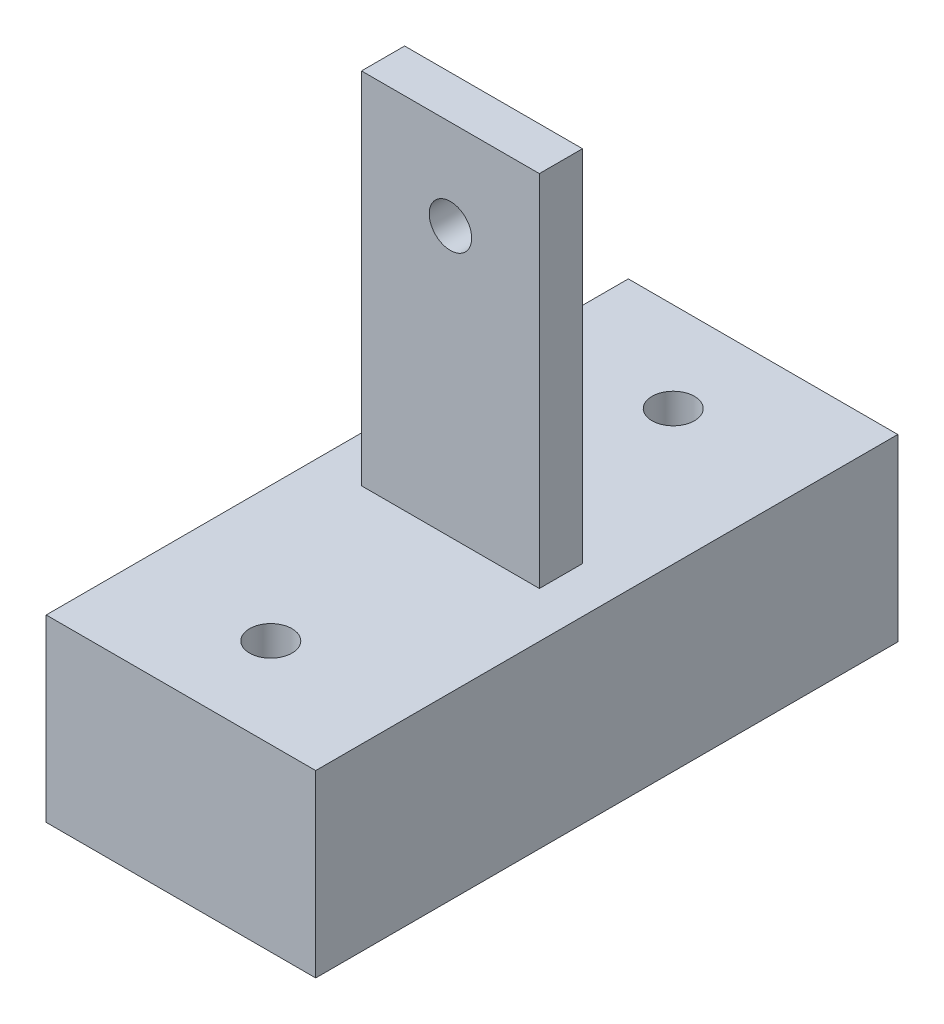
SolidWorks part; units mm, degrees
ref_plane "Front Plane" through (0, 0, 0) normal (0, 0, 1) x (1, 0, 0)
ref_plane "Top Plane" through (0, 0, 0) normal (0, 1, 0) x (1, 0, 0)
ref_plane "Right Plane" through (0, 0, 0) normal (1, 0, 0) x (0, 0, -1)
sketch "Sketch1" plane through (0, 0, 0) normal (1, 0, 0) x (0, 0, -1)
  line L1 (-20.574, 12.7) -> (20.574, 12.7)
  line L2 (-20.574, 12.7) -> (-20.574, 0)
  line L3 (-20.574, 0) -> (20.574, 0)
  line L4 (20.574, 12.7) -> (20.574, 0)
  line L5 (-1.524, 12.7) -> (1.524, 12.7)
  line L6 (-1.524, 12.7) -> (-1.524, 38.1)
  line L7 (-1.524, 38.1) -> (1.524, 38.1)
  line L8 (1.524, 12.7) -> (1.524, 38.1)
  point P10 (0, 38.1)
  point P14 (0, 0)
  dimension "D1" = 12.7
  dimension "D2" = 25.4
  dimension "D3" = 3.048
  dimension "D4" = 19.05
extrude "Boss-Extrude1" add sketch "Sketch1" along normal mid plane 19.05 contours L4 L1 L2 L3 region at (0, 6.35, 0)
extrude "Boss-Extrude2" add sketch "Sketch1<3>" along normal mid plane 12.573 contours L1 L8 L7 L6 region at (0, 25.4, 0)
sketch "Sketch1<3>" plane through (0, 0, 0) normal (1, 0, 0) x (0, 0, -1) same geometry as "Sketch1"
sketch "Sketch2" plane through (0, 0, 1.524) normal (0, 0, 1) x (1, 0, 0)
  line L0 (-6.2865, 19.05) -> (6.2865, 19.05) construction
  line L1 (-6.2865, 12.7) -> (-6.2865, 38.1) construction
  line L2 (6.2865, 12.7) -> (6.2865, 38.1) construction
  line L3 (9.525, 12.7) -> (-9.525, 12.7) construction
  circle A0 centre (0, 31.75) radius 1.5
  point P11 (0, 19.05)
  dimension "D3" = 3
  dimension "D1" = 6.35
  dimension "D2" = 12.7
extrude "Cut-Extrude1" cut sketch "Sketch2" against normal through all
sketch "Sketch4" plane through (0, 12.7, 0) normal (0, 1, 0) x (1, 0, 0)
  line L0 (0, -14.224) -> (0, 14.224) construction
  line L1 (6.2865, -1.524) -> (-6.2865, -1.524) construction
  circle A0 centre (0, -14.224) radius 1.5
  circle A2 centre (0, 14.224) radius 1.5
  point P2 (0, 0)
  dimension "D1" = 3
  dimension "D2" = 12.7
extrude "Cut-Extrude3" cut sketch "Sketch4" against normal through all
sketch "Sketch5" plane through (0, 0, 0) normal (0, -1, 0) x (1, 0, 0)
  circle A0 centre (0, 14.224) radius 4.7625
  circle A1 centre (0, -14.224) radius 4.7625
  circle A2 centre (0, 14.224) radius 1.5 construction
  circle A3 centre (0, -14.224) radius 1.5 construction
  dimension "D1" = 9.525
extrude "Cut-Extrude4" cut sketch "Sketch5" against normal blind 6.35
